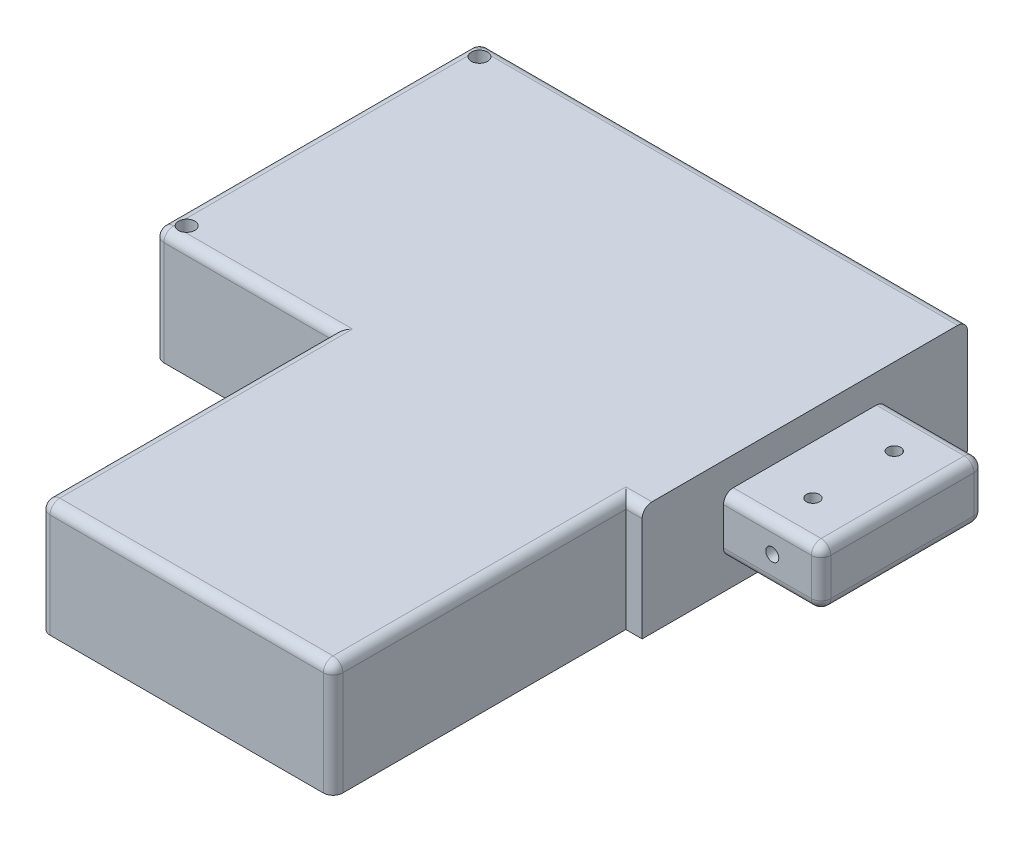
SolidWorks part; units mm, degrees
ref_plane "Front Plane" through (0, 0, 0) normal (0, 0, 1) x (1, 0, 0)
ref_plane "Top Plane" through (0, 0, 0) normal (0, 1, 0) x (1, 0, 0)
ref_plane "Right Plane" through (0, 0, 0) normal (1, 0, 0) x (0, 0, -1)
sketch "Sketch1" plane through (0, 0, 0) normal (0, 1, 0) x (1, 0, 0)
  line L0 (0, 0) -> (-108879.4816, 0) construction
  line L1 (0, 0) -> (0, -108879.4816) construction
  line L3 (-75, 50) -> (75, 50)
  line L4 (-75, 50) -> (-75, -50)
  line L5 (-75, -50) -> (75, -50)
  line L6 (75, 50) -> (75, -50)
  line L7 (-75, 50) -> (75, -50) construction
  line L8 (-75, -50) -> (75, 50) construction
  point P5 (0, 0)
  dimension "D1" = 150
  dimension "D2" = 100
extrude "Boss-Extrude1" add sketch "Sketch1" along normal blind 35
sketch "Sketch2" plane through (0, 35, 0) normal (0, 1, 0) x (1, 0, 0)
  line L0 (0, 0) -> (-50000, 0) construction
  line L1 (0, 0) -> (0, -50000) construction
  line L2 (65, -40) -> (65, 40) construction
  line L3 (65, 40) -> (-65, 40) construction
  line L4 (-65, 40) -> (-65, -40) construction
  line L5 (-65, -40) -> (65, -40) construction
  line L6 (75, -50) -> (75, 50)
  line L7 (75, 50) -> (-75, 50)
  line L8 (-75, 50) -> (-75, -50)
  line L9 (-75, -50) -> (75, -50)
  line L10 (75, -50) -> (75, 50) construction
  line L11 (75, 50) -> (-75, 50) construction
  line L12 (-75, 50) -> (-75, -50) construction
  line L13 (-75, -50) -> (75, -50) construction
  line L14 (-65, 40) -> (-75, 50) construction
  circle A0 centre (-70, 45) radius 2.5
  circle A1 centre (-70, -45) radius 2.5
  dimension "D3" = 5
  dimension "D1" = 0
  dimension "D2" = 10
extrude "Cut-Extrude1" cut sketch "Sketch2" against normal through all
sketch "Sketch3" plane through (0, 35, 0) normal (0, 1, 0) x (1, 0, 0)
  line L0 (0, 0) -> (-50000, 0) construction
  line L1 (0, 0) -> (0, -50000) construction
  line L2 (25, 0) -> (25, -50000) construction
  line L3 (-75, 50) -> (-75, -50) construction
  line L4 (-75, -50) -> (75, -50) construction
  line L5 (-20, -140) -> (70, -140)
  line L6 (-20, -140) -> (-20, -50)
  line L7 (-20, -50) -> (70, -50)
  line L8 (70, -140) -> (70, -50)
  line L9 (-20, -140) -> (70, -50) construction
  line L10 (-20, -50) -> (70, -140) construction
  point P9 (25, -95)
  dimension "D1" = 100
  dimension "D2" = 90
  dimension "D3" = 90
extrude "Boss-Extrude2" add sketch "Sketch3" against normal blind 35
sketch "Sketch4" plane through (0, 35, 0) normal (0, 1, 0) x (1, 0, 0)
  line L0 (0, 0) -> (-50000, 0) construction
  line L1 (0, 0) -> (0, -50000) construction
  line L2 (25, -130) -> (25, 49870) construction
  line L3 (-20, -140) -> (70, -140) construction
  line L4 (70, -50) -> (75, -50) construction
  circle A0 centre (25, -115) radius 18.5
  circle A1 centre (25, 0) radius 18.5
  point P9 (25, -140)
  dimension "D1" = 37
  dimension "D2" = 65
  dimension "D3" = 37
extrude "Cut-Extrude2" cut sketch "Sketch4" along normal blind 7 from surface starting at face at (-70, 0, -42.5)
sketch "Sketch5" plane through (0, 35, 0) normal (0, 1, 0) x (1, 0, 0)
  line L0 (0, 0) -> (50000, 0) construction
  line L1 (0, 0) -> (0, -50000) construction
  line L2 (25, -110) -> (25, 49890) construction
  circle A0 centre (25, -115) radius 14
  circle A1 centre (25, 0) radius 14
  dimension "D1" = 28
  dimension "D2" = 28
extrude "Cut-Extrude3" cut sketch "Sketch5" along normal blind 25 from surface starting at face at (25, 0, 133.5)
sketch "Sketch6" plane through (75, 0, 0) normal (1, 0, 0) x (0, 0, -1)
  line L0 (0, 0) -> (0, 50000) construction
  line L1 (-50, 0) -> (50, 0) construction
  line L2 (50, 17.5) -> (-49950, 17.5) construction
  line L4 (50, 35) -> (50, 0) construction
  line L10 (-25, 26.25) -> (25, 26.25)
  line L11 (-25, 26.25) -> (-25, 8.75)
  line L12 (-25, 8.75) -> (25, 8.75)
  line L13 (25, 26.25) -> (25, 8.75)
  line L14 (-25, 26.25) -> (25, 8.75) construction
  line L15 (-25, 8.75) -> (25, 26.25) construction
  point P4 (0, 0)
  point P9 (50, 17.5)
  point P10 (0, 17.5)
  dimension "D1" = 50
  dimension "D2" = 17.5
extrude "Boss-Extrude3" add sketch "Sketch6" along normal blind 30
sketch "Sketch7" plane through (0, 26.25, 0) normal (0, 1, 0) x (1, 0, 0)
  line L0 (0, 0) -> (50000, 0) construction
  line L1 (0, 0) -> (0, -50000) construction
  line L2 (90, 25) -> (90, -49975) construction
  line L3 (105, 25) -> (75, 25) construction
  circle A0 centre (90, 12.5) radius 2
  circle A1 centre (90, -12.5) radius 2
  point P9 (90, 25)
  dimension "D1" = 4
  dimension "D2" = 12.5
extrude "Cut-Extrude4" cut sketch "Sketch7" against normal blind 8
sketch "Sketch8" plane through (0, 0, -25) normal (0, 0, -1) x (-1, 0, 0)
  line L0 (0, 0) -> (0, -50000) construction
  line L1 (-95, 17.5) -> (49905, 17.5) construction
  line L2 (-105, 8.75) -> (-105, 26.25) construction
  line L3 (-90, 26.25) -> (-90, -49973.75) construction
  line L4 (-105, 26.25) -> (-75, 26.25) construction
  circle A0 centre (-90, 17.5) radius 2
  point P7 (-105, 17.5)
  point P12 (-90, 26.25)
  dimension "D1" = 4
extrude "Cut-Extrude5" cut sketch "Sketch8" against normal blind 8 contours A0
mirror "Mirror1" about plane through (0, 0, 0) normal (0, 0, 1) of "Cut-Extrude5"
fillet "Fillet1" radius 3 19 edges at (25, 35, 140) (70, 17.5, 140) (-20, 17.5, 140) (70, 35, 95) (72.5, 35, 50) (-20, 35, 95) (-47.5, 35, 50) (0, 35, -50) (-75, 35, 0) (-75, 17.5, -50) (-75, 17.5, 50) (105, 17.5, -25) (105, 8.75, 0) (105, 17.5, 25) (105, 26.25, 0) (90, 8.75, -25) (90, 26.25, -25) (90, 8.75, 25) (90, 26.25, 25)
